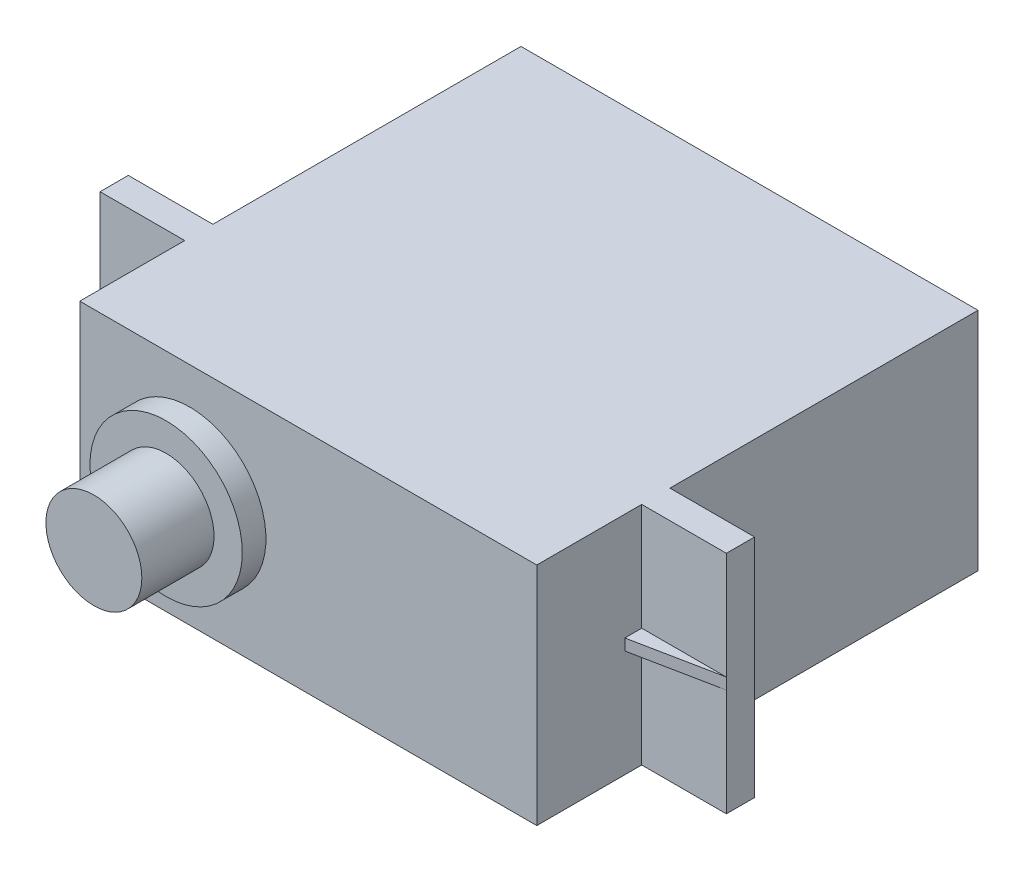
SolidWorks part; units mm, degrees
ref_plane "Front Plane" through (0, 0, 0) normal (0, 0, 1) x (1, 0, 0)
ref_plane "Top Plane" through (0, 0, 0) normal (0, 1, 0) x (1, 0, 0)
ref_plane "Right Plane" through (0, 0, 0) normal (1, 0, 0) x (0, 0, -1)
sketch "Sketch1" plane through (0, 0, 0) normal (0, 0, 1) x (1, 0, 0)
  line L1 (0, 0) -> (40.5, 0)
  line L2 (0, 0) -> (0, 20)
  line L3 (0, 20) -> (40.5, 20)
  line L4 (40.5, 0) -> (40.5, 20)
  dimension "D1" = 40.5
  dimension "D2" = 20
extrude "Boss-Extrude1" add sketch "Sketch1" along normal blind 39.1
sketch "Sketch2" plane through (0, 0, 39.1) normal (0, 0, 1) x (1, 0, 0)
  line L0 (0, 10) -> (40.5, 10) construction
  line L1 (0, 20) -> (0, 0) construction
  line L2 (40.5, 0) -> (40.5, 20) construction
  circle A0 centre (9.75, 10) radius 6.75
  point P8 (3, 10)
  dimension "D1" = 13.5
  dimension "D2" = 3
extrude "Boss-Extrude2" add sketch "Sketch2" along normal blind 2.1
sketch "Sketch3" plane through (0, 0, 41.2) normal (0, 0, 1) x (1, 0, 0)
  circle A0 centre (9.75, 10) radius 4.25
  circle A1 centre (9.75, 10) radius 6.75 construction
  dimension "D1" = 8.5
extrude "Boss-Extrude3" add sketch "Sketch3" along normal blind 6.4
sketch "Sketch4" plane through (40.5, 0, 0) normal (1, 0, 0) x (0, 0, -1)
  line L0 (-39.1, 20) -> (0, 20) construction
  line L1 (-27.3, 20) -> (-29.8, 20)
  line L2 (-27.3, 20) -> (-27.3, 0)
  line L3 (-27.3, 0) -> (-29.8, 0)
  line L4 (-29.8, 20) -> (-29.8, 0)
  line L5 (-39.1, 0) -> (0, 0) construction
  line L7 (0, 0) -> (0, 20) construction
  dimension "D1" = 27.3
  dimension "D2" = 2.5
extrude "Boss-Extrude4" add sketch "Sketch4" along normal blind 7.5
chamfer "Chamfer1" distance 1.5 distance2 7.5 1 edges at (40.5, 10, 29.8) first distance on face at (40.5, 10, 34.45)
sketch "Sketch5" plane through (0, 0, 0) normal (0, -1, 0) x (1, 0, 0)
  line L0 (48, 29.8) -> (40.5, 29.8)
  line L1 (40.5, 31.3) -> (40.5, 29.8)
  line L2 (48, 29.8) -> (40.5, 31.3)
extrude "Cut-Extrude1" cut sketch "Sketch5" against normal blind 9.5
ref_plane "Plane1" through (0, 10, 0) normal (0, 1, 0) x (1, 0, 0)
mirror "Mirror1" about plane through (0, 10, 0) normal (0, 1, 0) of "Cut-Extrude1"
ref_plane "Plane2" through (20.25, 0, 0) normal (1, 0, 0) x (0, 0, -1)
mirror "Mirror11" about plane through (20.25, 0, 0) normal (1, 0, 0) of "Boss-Extrude4"
chamfer "Chamfer2" distance 7.5 distance2 1.5 1 edges at (0, 10, 29.8) first distance on face at (-3.75, 10, 29.8)
mirror "Mirror19" about plane through (20.25, 0, 0) normal (1, 0, 0) of "Mirror1", "Cut-Extrude1"
